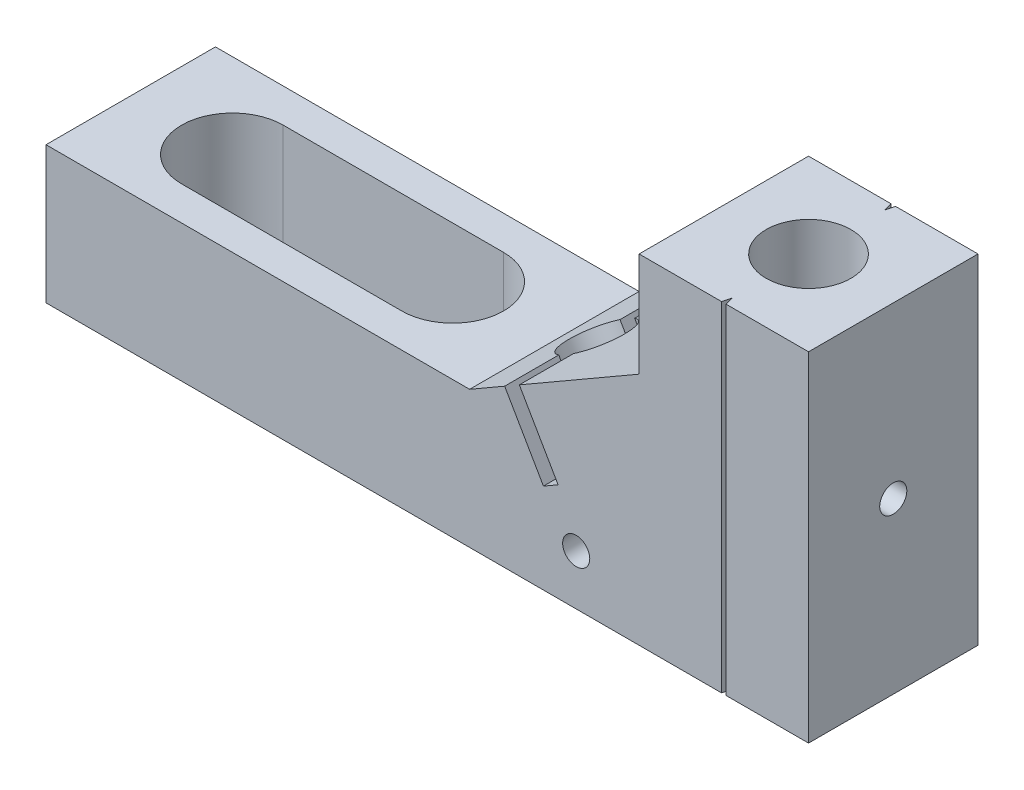
SolidWorks part; units mm, degrees
ref_plane "Front Plane" through (0, 0, 0) normal (0, 0, 1) x (1, 0, 0)
ref_plane "Top Plane" through (0, 0, 0) normal (0, 1, 0) x (1, 0, 0)
ref_plane "Right Plane" through (0, 0, 0) normal (1, 0, 0) x (0, 0, -1)
sketch "Sketch1" plane through (0, 0, 0) normal (0, 1, 0) x (1, 0, 0)
  line L1 (-13.6389, 9.0278) -> (6.3611, 9.0278)
  line L2 (-13.6389, 9.0278) -> (-13.6389, -0.9722)
  line L3 (-13.6389, -0.9722) -> (6.3611, -0.9722)
  line L4 (6.3611, 9.0278) -> (6.3611, -0.9722)
  dimension "D1" = 20
  dimension "D2" = 10
extrude "Boss-Extrude1" add sketch "Sketch1" along normal blind 20
sketch "Sketch2" plane through (0, 20, 0) normal (0, 1, 0) x (1, 0, 0)
  line L0 (-13.6389, 4.0278) -> (6.3611, 4.0278) construction
  line L1 (-13.6389, 9.0278) -> (-13.6389, -0.9722) construction
  line L2 (6.3611, -0.9722) -> (6.3611, 9.0278) construction
  line L3 (1.4951, -0.9722) -> (1.3611, -0.4722)
  line L4 (-13.6389, -0.9722) -> (6.3611, -0.9722) construction
  line L5 (1.3611, -0.4722) -> (1.2271, -0.9722)
  line L6 (1.4951, -0.9722) -> (1.2271, -0.9722)
  line L7 (1.3611, 8.5278) -> (1.2271, 9.0278)
  line L8 (1.4951, 9.0278) -> (1.3611, 8.5278)
  line L9 (1.4951, 9.0278) -> (1.2271, 9.0278)
  circle A0 centre (1.3611, 4.0278) radius 2.5
  dimension "D1" = 5
  dimension "D2" = 5
  dimension "D3" = 30
  dimension "D4" = 0.5
extrude "Cut-Extrude1" cut sketch "Sketch2" against normal through all
sketch "Sketch3" plane through (0, 0, 0.9722) normal (0, 0, 1) x (1, 0, 0)
  line L0 (-13.6389, 20) -> (-3.6389, 20)
  line L1 (-13.6389, 20) -> (1.2271, 20) construction
  line L2 (-3.6389, 13.8564) -> (-10.7059, 9.7763)
  line L3 (-13.6389, 20) -> (-13.6389, 0) construction
  line L4 (-13.6389, 8.0829) -> (-13.6389, 20)
  line L5 (-3.6389, 13.8564) -> (-3.6389, 20)
  line L6 (-13.6389, 0) -> (1.2271, 0) construction
  line L7 (-11.1389, 9.5263) -> (-5.6389, 0) construction
  line L8 (6.3611, 20) -> (6.3611, 0) construction
  line L10 (-10.7059, 9.7763) -> (-8.4174, 5.8125)
  line L11 (-11.5719, 9.2763) -> (-9.2834, 5.3125)
  line L12 (-8.4174, 5.8125) -> (-9.2834, 5.3125)
  line L13 (-11.5719, 9.2763) -> (-13.6389, 8.0829)
  point P1 (-8.8504, 5.5625)
  point P17 (-8.3889, 4.7631)
  dimension "D1" = 30
  dimension "D2" = 11
  dimension "D3" = 12
  dimension "D4" = 10
  dimension "D5" = 1
  dimension "D6" = 4.577
extrude "Cut-Extrude2" cut sketch "Sketch3" against normal through all
sketch "Sketch5" plane through (-6.9097, 11.968, 0) normal (-0.5, 0.866, 0) x (0.866, 0.5, 0)
  line L0 (-4.3834, 9.0278) -> (-4.3834, -0.9722) construction
  line L1 (-4.3834, 4.0278) -> (-5.3834, 4.0278) construction
  line L2 (-5.3834, 9.0278) -> (-5.3834, -0.9722) construction
  circle A0 centre (-4.8834, 4.0278) radius 1.875
  point P5 (-4.3834, 4.0278)
  dimension "D1" = 3.75
extrude "Cut-Extrude5" cut sketch "Sketch5" against normal through all
sketch "Sketch6" plane through (6.3611, 0, 0) normal (1, 0, 0) x (0, 0, -1)
  line L0 (9.0278, 20) -> (9.0278, 0) construction
  line L1 (-0.9722, 20) -> (9.0278, 20) construction
  point P0 (4.0278, 10)
  point P4 (9.0278, 10)
  point P8 (4.0278, 20)
hole_wizard "M2x0.4 Tapped Hole1" positions "Sketch7" profile "Sketch8" tap size "M2x0.4" standard "BSI"
sketch "Sketch7" plane through (6.3611, 0, 0) normal (1, 0, 0) x (0, 0, -1)
  point P0 (4.0278, 10)
sketch "Sketch8" plane through (6.3611, 10, -4.0278) normal (0, 1, 0) x (0, 0, -1)
  line L0 (0, 0) -> (0, 6.4807)
  line L1 (0, 6.4807) -> (0.8, 6)
  line L2 (0.8, 6) -> (0.8, 0)
  line L5 (0.8, 0) -> (0, 0)
  line L10 (0, 6.4807) -> (-0.8, 6) construction
  line L11 (0, -6.35) -> (0, 107.95) construction
  dimension "Tap Drill Dia." = 1.6
  dimension "Tap Drill Depth" = 6
  dimension "Drill Angle" = 118
cosmetic thread "Hole Thread1" parameters "D1"=4, "D2"=2
hole_wizard "M2x0.4 Tapped Hole2" positions "Sketch9" profile "Sketch10" tap size "M2x0.4" standard "BSI"
sketch "Sketch9" plane through (0, 0, 0.9722) normal (0, 0, 1) x (1, 0, 0)
  line L0 (-9.2834, 5.3125) -> (-8.4174, 5.8125) construction
  line L1 (-7.3504, 2.9644) -> (-8.8504, 5.5625) construction
  point P0 (-7.3504, 2.9644)
  dimension "D1" = 3
sketch "Sketch10" plane through (-7.3504, 2.9644, 0.9722) normal (1, 0, 0) x (0, -1, 0)
  line L0 (0, 0) -> (0, 6.4807)
  line L1 (0, 6.4807) -> (0.8, 6)
  line L2 (0.8, 6) -> (0.8, 0)
  line L5 (0.8, 0) -> (0, 0)
  line L10 (0, 6.4807) -> (-0.8, 6) construction
  line L11 (0, -6.35) -> (0, 107.95) construction
  dimension "Tap Drill Dia." = 1.6
  dimension "Tap Drill Depth" = 6
  dimension "Drill Angle" = 118
cosmetic thread "Hole Thread2" parameters "D1"=4, "D2"=2
sketch "Sketch14" plane through (-13.6389, 0, 0) normal (-1, 0, 0) x (0, 0, 1)
  line L4 (0.9722, 0) -> (0.9722, 8.0829)
  line L5 (0.9722, 8.0829) -> (-9.0278, 8.0829)
  line L6 (-9.0278, 8.0829) -> (-9.0278, 0)
  line L7 (-9.0278, 0) -> (0.9722, 0)
  line L8 (0.9722, 0) -> (0.9722, 8.0829)
  line L9 (0.9722, 8.0829) -> (-9.0278, 8.0829)
  line L10 (-9.0278, 8.0829) -> (-9.0278, 0)
  line L11 (-9.0278, 0) -> (0.9722, 0)
  dimension "D1" = 0
extrude "Boss-Extrude3" add sketch "Sketch14" along normal blind 25
sketch "Sketch15" plane through (0, 8.0829, 0) normal (0, 1, 0) x (1, 0, 0)
  line L0 (-13.6389, 9.0278) -> (-13.6389, -0.9722) construction
  line L1 (-38.6389, -0.9722) -> (-38.6389, 9.0278) construction
  line L2 (-32.6389, 4.0278) -> (-19.6389, 4.0278) construction
  line L3 (-38.6389, -0.9722) -> (-13.6389, -0.9722) construction
  line L4 (-19.6389, 1.0278) -> (-32.6389, 1.0278)
  line L5 (-32.6389, 7.0278) -> (-19.6389, 7.0278)
  line L6 (-38.6389, 9.0278) -> (-13.6389, 9.0278) construction
  arc A0 (-19.6389, 1.0278) -> (-19.6389, 7.0278) centre (-19.6389, 4.0278) ccw
  arc A1 (-32.6389, 7.0278) -> (-32.6389, 1.0278) centre (-32.6389, 4.0278) ccw
  point P2 (-26.1389, 4.0278)
  point P5 (-13.6389, 4.0278)
  point P11 (-38.6389, 4.0278)
  point P13 (-26.1389, -0.9722)
  dimension "D1" = 6
  dimension "D2" = 6
  dimension "D3" = 13
extrude "Cut-Extrude7" cut sketch "Sketch15" against normal up to next
